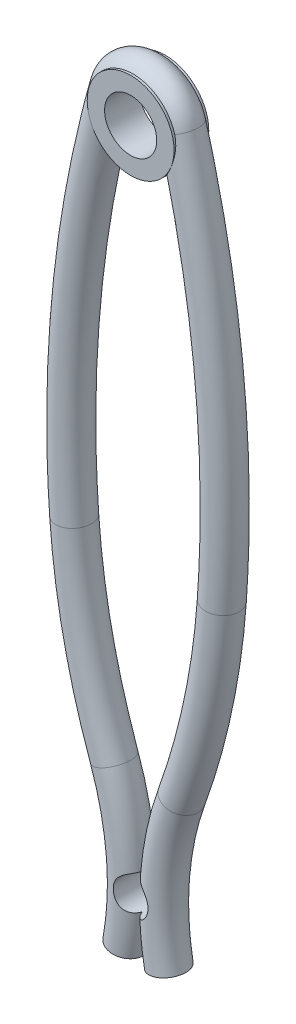
SolidWorks part; units mm, degrees
ref_plane "Front Plane" through (0, 0, 0) normal (0, 0, 1) x (1, 0, 0)
ref_plane "Top Plane" through (0, 0, 0) normal (0, 1, 0) x (1, 0, 0)
ref_plane "Right Plane" through (0, 0, 0) normal (1, 0, 0) x (0, 0, -1)
sketch "Sketch4" plane through (0, 0, 0) normal (0, 0, 1) x (1, 0, 0)
  line L0 (0, 0) -> (0, 33.7191) construction
  line L1 (0, 33.7191) -> (36.5815, 33.7191) construction
  arc A0 (2.4436, 31.8723) -> (5.3974, 3.1569) centre (-77.8013, 9.1083) cw
  arc A1 (5.3974, 3.1569) -> (2.4661, -10.7178) centre (-46.4652, 6.8667) cw
  arc A2 (2.4661, -10.7178) -> (1.524, -21.9328) centre (22.9736, -18.0877) ccw
  arc A3 (2.4436, 31.8723) -> (0, 33.7191) centre (0, 31.1791) ccw
  dimension "D1" = 2.54
  dimension "D4" = 21.7915
  dimension "D5" = 1.524
sketch "Sketch5" plane through (0, 0, 0) normal (1, 0, 0) x (0, 0, -1)
  circle A0 centre (0, 33.7191) radius 1.27
  dimension "D1" = 2.54
sweep "Sweep1" add profiles "Sketch5" path "Sketch4"
mirror "Mirror1" about plane through (0, 0, 0) normal (1, 0, 0) of "Sweep1"
sketch "Sketch6" plane through (0, 0, 0) normal (0, 0, 1) x (1, 0, 0)
  circle A0 centre (0, -17.78) radius 1.27
  dimension "D1" = 2.54
  dimension "D2" = 17.78
extrude "Cut-Extrude1" cut sketch "Sketch6" against normal through all and the other way through all
ref_axis "Axis1" through (0, 31.1791, 21.3369) along (0, 0, -1)
sketch "Sketch7" plane through (0, 0, 0) normal (0, 0, 1) x (1, 0, 0)
  circle A2 centre (0, 31.1791) radius 3.175
  dimension "D1" = 6.35
extrude "Extrude1" add sketch "Sketch7" along normal mid plane 2.54
sketch "Sketch8" plane through (0, 0, 1.27) normal (0, 0, 1) x (1, 0, 0)
  circle A0 centre (0, 31.1791) radius 1.905
  dimension "D1" = 3.81
extrude "Cut-Extrude2" cut sketch "Sketch8" against normal through all
